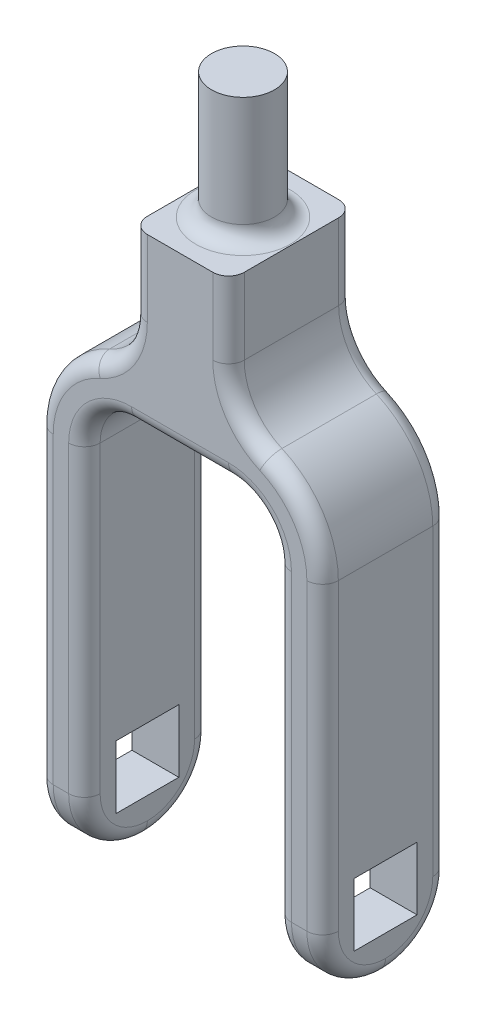
SolidWorks part; units mm, degrees
ref_plane "Front Plane" through (0, 0, 0) normal (0, 0, 1) x (1, 0, 0)
ref_plane "Top Plane" through (0, 0, 0) normal (0, 1, 0) x (1, 0, 0)
ref_plane "Right Plane" through (0, 0, 0) normal (1, 0, 0) x (0, 0, -1)
sketch "Sketch1" plane through (0, 0, 0) normal (0, 0, 1) x (1, 0, 0)
  line L0 (0, 45.6642) -> (0, -42.6534) construction
  line L1 (3.175, -30) -> (-3.175, -30) construction
  line L2 (3.175, -30) -> (3.175, 30) construction
  line L3 (3.175, 30) -> (-3.175, 30) construction
  line L4 (-3.175, -30) -> (-3.175, 30) construction
  line L5 (30.7615, 0) -> (-76.2337, 0) construction
  line L6 (9.652, -6.985) -> (9.652, 30)
  line L7 (-9.652, -6.985) -> (-9.652, 30)
  line L12 (-4.8895, 34.7625) -> (4.8895, 34.7625)
  line L13 (14.3828, -6.985) -> (14.3828, 30)
  line L14 (-4.8895, 39.4933) -> (4.8895, 39.4932)
  line L15 (-14.3827, -6.985) -> (-14.3827, 30)
  line L16 (-14.3827, -6.985) -> (-9.652, -6.985)
  line L17 (9.652, -6.985) -> (15.0801, -6.985)
  arc A4 (9.652, 30) -> (4.8895, 34.7625) centre (4.8895, 30) ccw
  arc A5 (-4.8895, 34.7625) -> (-9.652, 30) centre (-4.8895, 30) ccw
  arc A6 (14.3828, 30) -> (4.8895, 39.4932) centre (4.8895, 30) ccw
  arc A7 (-4.8895, 39.4933) -> (-14.3827, 30) centre (-4.8895, 30) ccw
  point P0 (0, 0)
  dimension "D3" = 6.985
  dimension "D1" = 9.652
  dimension "D2" = 4.7307
extrude "Boss-Extrude1" add sketch "Sketch1" along normal blind 12.7 contours L14 A7 L15 L16 L7 A5 L12 A4 L6 L17 L13 A6 region at (10.1986, 11.5075, 0)
sketch "Sketch2" plane through (0, 39.4933, 0) normal (0, 1, 0) x (1, 0, 0)
  line L0 (-4.8895, 0) -> (4.8895, 0) construction
  line L1 (4.8895, -12.7) -> (-4.8895, -12.7)
  line L2 (4.8895, -12.7) -> (4.8895, 0)
  line L3 (4.8895, 0) -> (-4.8895, 0)
  line L4 (-4.8895, -12.7) -> (-4.8895, 0)
  line L5 (4.8895, -12.7) -> (-4.8895, 0) construction
  line L6 (4.8895, 0) -> (-4.8895, -12.7) construction
  line L7 (-4.8895, -12.7) -> (-4.8895, 0) construction
  line L8 (-4.8895, -12.7) -> (4.8895, -12.7) construction
  line L9 (4.8895, -12.7) -> (4.8895, 0) construction
  point P0 (0, -6.35)
extrude "Boss-Extrude2" add sketch "Sketch2" along normal blind 12.7
fillet "Fillet1" radius 6.35 2 edges at (-4.8895, 39.4933, 6.35) (4.8895, 39.4933, 6.35)
sketch "Sketch3" plane through (0, 52.1933, 0) normal (0, 1, 0) x (1, 0, 0)
  circle A0 centre (0, -6.35) radius 3.175
  dimension "D1" = 6.35
extrude "Boss-Extrude3" add sketch "Sketch3" along normal blind 12.7
sketch "Sketch4" plane through (-14.3827, 0, 0) normal (-1, 0, 0) x (0, 0, 1)
  line L0 (12.7, -6.985) -> (0, -6.985) construction
  line L1 (9.525, -3.175) -> (3.175, -3.175)
  line L2 (9.525, -3.175) -> (9.525, 3.175)
  line L3 (9.525, 3.175) -> (3.175, 3.175)
  line L4 (3.175, -3.175) -> (3.175, 3.175)
  line L5 (9.525, -3.175) -> (3.175, 3.175) construction
  line L6 (9.525, 3.175) -> (3.175, -3.175) construction
  point P0 (6.35, 0)
  point P5 (0, 0)
  point P8 (6.35, -6.985)
  dimension "D1" = 6.35
  dimension "D2" = 6.985
extrude "Cut-Extrude1" cut sketch "Sketch4" against normal blind 43.688
fillet "Fillet2" radius 6.35 4 edges at (12.0174, -6.985, 12.7) (12.0174, -6.985, 0) (-12.0174, -6.985, 12.7) (-12.0174, -6.985, 0)
fillet "Fillet5" radius 1.5875 34 edges at (-4.8895, 48.3541, 0) (-5.9252, 41.0393, 0) (-12.8344, 35.1962, 0) (-14.3827, 14.6825, 0) (-14.3827, -5.1251, 1.8599) (-14.3827, -5.1251, 10.8401) (-14.3827, 14.6825, 12.7) (-12.8344, 35.1962, 12.7) (-5.9252, 41.0393, 12.7) (4.8895, 48.3541, 0) (5.9252, 41.0393, 0) (12.8344, 35.1962, 0) (14.3828, 14.6825, 0) (14.3828, -5.1251, 1.8599) (14.3828, -5.1251, 10.8401) (14.3828, 14.6825, 12.7) (12.8344, 35.1962, 12.7) (5.9252, 41.0393, 12.7) (-4.8895, 48.3541, 12.7) (4.8895, 48.3541, 12.7) (-9.652, -5.1251, 10.8401) (-9.652, -5.1251, 1.8599) (-9.652, 14.6825, 0) (-8.2571, 33.3676, 0) (0, 34.7625, 0) (8.2571, 33.3676, 0) (9.652, 14.6825, 0) (9.652, -5.1251, 1.8599) (9.652, -5.1251, 10.8401) (9.652, 14.6825, 12.7) (8.2571, 33.3676, 12.7) (0, 34.7625, 12.7) (-8.2571, 33.3676, 12.7) (-9.652, 14.6825, 12.7)
fillet "Fillet7" radius 1.5875 1 edges at (-3.175, 52.1933, 6.35)
